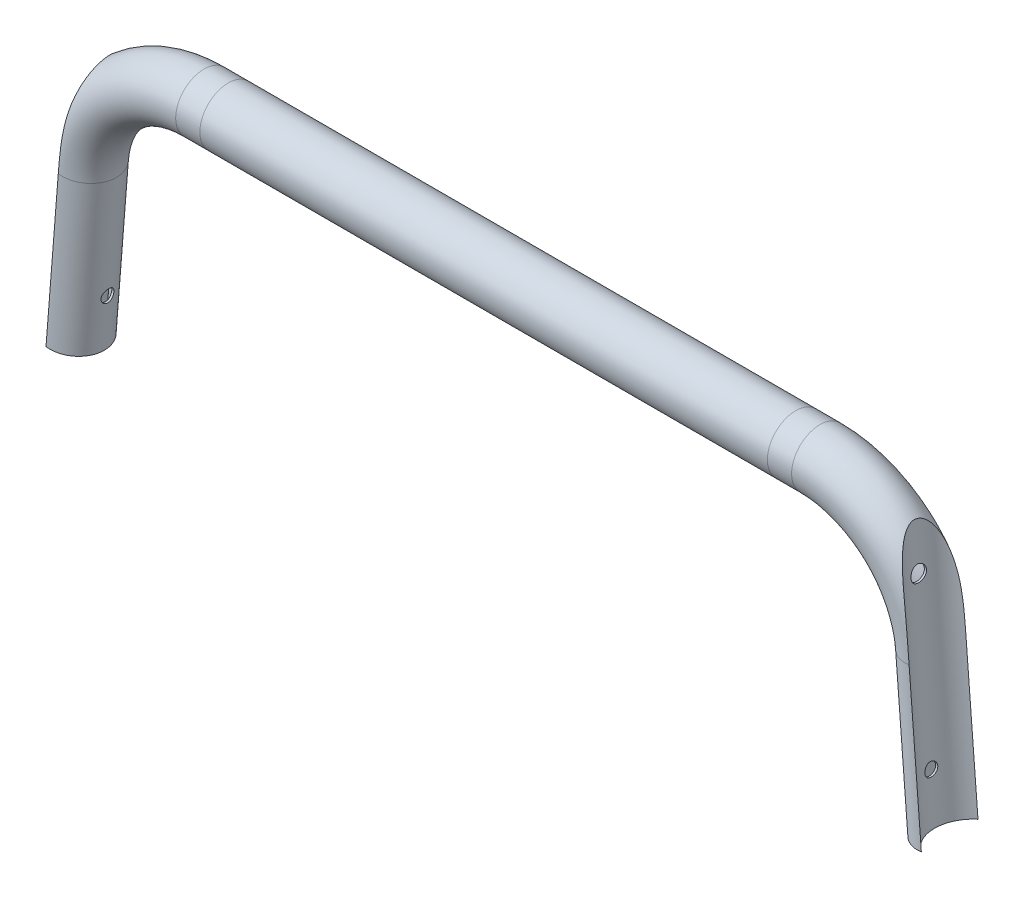
SolidWorks part; units mm, degrees
ref_plane "Front Plane" through (0, 0, 0) normal (0, 0, 1) x (1, 0, 0)
ref_plane "Top Plane" through (0, 0, 0) normal (0, 1, 0) x (1, 0, 0)
ref_plane "Right Plane" through (0, 0, 0) normal (1, 0, 0) x (0, 0, -1)
sketch "Sketch1" plane through (0, 0, 0) normal (0, 0, 1) x (1, 0, 0)
  line L0 (-110, 0) -> (110, 0)
  line L1 (0, 0) -> (0, -80) construction
  line L3 (-169, -101.9) -> (-164.244, -41.4693)
  line L4 (-119.3827, 0) -> (-110, 0)
  line L5 (169, -101.9) -> (164.244, -41.4693)
  line L6 (119.3827, 0) -> (110, 0)
  arc A0 (164.244, -41.4693) -> (119.3827, 0) centre (119.3827, -45) ccw
  arc A1 (-119.3827, 0) -> (-164.244, -41.4693) centre (-119.3827, -45) ccw
  point P4 (0, 0)
  point P11 (0, -80)
  dimension "D5" = 45
  dimension "D1" = 220
  dimension "D2" = 101.9
  dimension "D3" = 94.5
  dimension "D4" = 94.5
  dimension "D6" = 101.9
  dimension "D7" = 338
ref_plane "Plane1" through (-169, -101.9, 0) normal (-0.0785, -0.9969, 0) x (-0.9969, 0.0785, 0)
sketch "Sketch2" plane through (-169, -101.9, 0) normal (-0.0785, -0.9969, 0) x (-0.9969, 0.0785, 0)
  line L0 (-41.4693, 0) -> (0, 0) construction
  circle A0 centre (0, 0) radius 11
  circle A1 centre (0, 0) radius 10.2
  dimension "D1" = 0.8
sweep "Sweep1" add profiles "Sketch2" path "Sketch1"
sketch "Sketch3" plane through (9.0107, -114.4914, 0) normal (0.0785, -0.9969, 0) x (0.9969, 0.0785, 0)
  line L0 (160.484, 0) -> (168.484, 0) construction
  circle A0 centre (168.484, 0) radius 13.2
  dimension "D2" = 26.4
  dimension "D1" = 8
extrude "Cut-Extrude1" cut sketch "Sketch3" against normal through all
mirror "Mirror1" about plane through (0, 0, 0) normal (1, 0, 0) of "Cut-Extrude1"
sketch "Sketch6" plane through (9.0107, -114.4914, 0) normal (0.0785, -0.9969, 0) x (0.9969, 0.0785, 0)
  line L0 (160.484, 0) -> (168.484, 0) construction
  arc A0 (161.6458, 11.2906) -> (161.6458, -11.2906) centre (168.484, 0) ccw
  arc A2 (160.2858, 11.3485) -> (160.2858, -11.3485) centre (168.484, 0) ccw
  arc A3 (160.2858, -11.3485) -> (161.6458, -11.2906) centre (160.484, 0) ccw
  circle A4 centre (168.484, 0) radius 14 construction
  circle A5 centre (168.484, 0) radius 13.2 construction
  arc A6 (161.6458, 11.2906) -> (160.2858, 11.3485) centre (160.484, 0) ccw
  dimension "D1" = 0.8
extrude "Boss-Extrude1" add sketch "Sketch6" against normal up to next
mirror "Mirror2" about plane through (0, 0, 0) normal (1, 0, 0) of "Boss-Extrude1"
sketch "Sketch7" plane through (9.0107, -114.4914, 0) normal (0.0785, -0.9969, 0) x (0.9969, 0.0785, 0)
  line L0 (149.484, 0) -> (160.484, 0)
  arc A0 (161.1565, 10.9794) -> (161.1565, -10.9794) centre (160.484, 0) ccw construction
ref_plane "Plane2" through (169, -101.9, 0) normal (0.9969, 0.0785, 0) x (0, 0, -1)
sketch "Sketch8" plane through (169, -101.9, 0) normal (0.9969, 0.0785, 0) x (0, 0, -1)
  line L0 (0, 0.0022) -> (0, 19.1022) construction
  circle A0 centre (0, 19.1022) radius 2.5
  dimension "D1" = 19.1
extrude "Cut-Extrude2" cut sketch "Sketch8" against normal up to surface (326.5997 mm away) up to face at (161.4742, -72.0898, 0)
mirror "Mirror3" about plane through (0, 0, 0) normal (1, 0, 0) of "Cut-Extrude2"
ref_plane "Plane3" through (180, 0, 0) normal (1, 0, 0) x (0, 0, -1)
sketch "Sketch9" plane through (180, 0, 0) normal (1, 0, 0) x (0, 0, -1)
  circle A0 centre (0, -20) radius 3
  dimension "D1" = 20
extrude "Cut-Extrude3" cut sketch "Sketch9" against normal up to next
